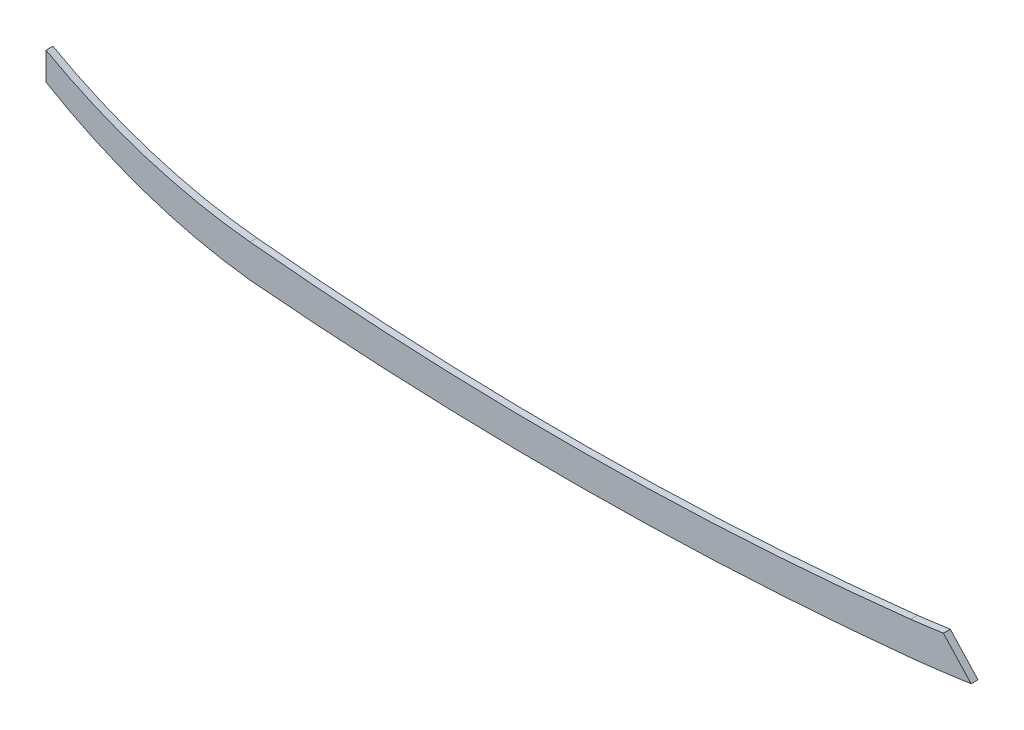
SolidWorks part; units mm, degrees
material "Balsa"
ref_plane "Front Plane" through (0, 0, 0) normal (0, 0, 1) x (1, 0, 0)
ref_plane "Top Plane" through (0, 0, 0) normal (0, 1, 0) x (1, 0, 0)
ref_plane "Right Plane" through (0, 0, 0) normal (1, 0, 0) x (0, 0, -1)
sketch "Sketch2" plane through (0, 0, 0) normal (0, 0, 1) x (1, 0, 0)
  line L0 (0, -94.4694) -> (0, -81.7694)
  line L1 (0, -94.4694) -> (93.98, -94.4694) construction
  line L2 (93.98, -126.4975) -> (93.98, -111.2575) construction
  line L3 (349.6407, -137.6462) -> (348.9613, -137.618) construction
  line L4 (349.6407, -137.6462) -> (354.8905, -137.8645) construction
  line L5 (93.98, -94.4694) -> (93.98, -126.4975) construction
  line L6 (400.2036, -124.7658) -> (400.2036, -94.4694) construction
  line L7 (590.8643, -81.3536) -> (588.5933, -68.8583)
  line L8 (0, 0) -> (672.417, 0) construction
  line L10 (93.98, -94.4694) -> (590.8643, -94.4694) construction
  line L11 (590.8643, -94.4694) -> (590.8643, -81.3536) construction
  line L12 (400.2036, -124.7658) -> (396.2207, -94.4694) construction
  line L13 (435.1113, -131.2328) -> (378.9266, -70.3516) construction
  line L14 (435.1113, -131.2328) -> (378.9266, -70.3516)
  arc A0 (0, -94.4694) -> (93.98, -126.4975) centre (121.7349, 108.8411) ccw
  arc A3 (93.98, -126.4975) -> (400.2036, -124.7658) centre (237.9716, 1487.1243) ccw
  arc A6 (400.2036, -124.7658) -> (590.8643, -81.3536) centre (300.4984, 753.5129) ccw
  arc A7 (93.98, -111.2575) -> (398.2172, -109.6558) centre (238.5005, 1332.7838) ccw
  arc A10 (0, -81.7694) -> (93.98, -111.2575) centre (118.1544, 130.2915) ccw
  arc A11 (398.2172, -109.6558) -> (588.5933, -68.8583) centre (253.2315, 1031.484) ccw
  dimension "D3" = 236.9696
  dimension "D4" = 30.2963
  dimension "D5" = 400.2036
  dimension "D6" = 79.699
  dimension "D7" = 82.511
  dimension "D8" = 15.24
  dimension "D11" = 242.7557
  dimension "D14" = 1620.0336
  dimension "D15" = 883.92
  dimension "D16" = 15.24
  dimension "D18" = 1150.3133
  dimension "D1" = 12.7
  dimension "D2" = 81.7694
  dimension "D9" = 32.028
  dimension "D10" = 93.98
  dimension "D12" = 13.1158
  dimension "D13" = 496.8843
  dimension "D17" = 12.7
extrude "Boss-Extrude1" add sketch "Sketch2" along normal blind 3.175 contours A11 A7 A10 L0 A0 A3 A6 L14 region at (212.2047, -119.3973, 0)
